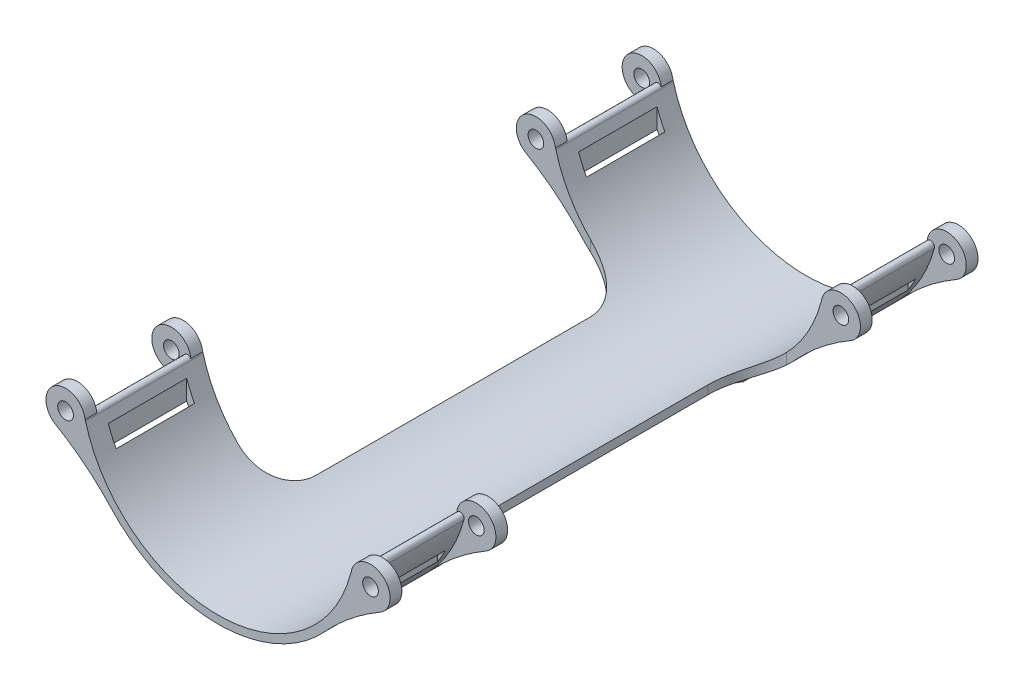
SolidWorks part; units mm, degrees
ref_plane "Front Plane" through (0, 0, 0) normal (0, 0, 1) x (1, 0, 0)
ref_plane "Top Plane" through (0, 0, 0) normal (0, 1, 0) x (1, 0, 0)
ref_plane "Right Plane" through (0, 0, 0) normal (1, 0, 0) x (0, 0, -1)
sketch "Sketch1" plane through (0, 0, 0) normal (0, 0, 1) x (1, 0, 0)
  line L0 (0, 0) -> (-33.8074, -9.0587) construction
  line L1 (33.8074, -9.0587) -> (0, 0) construction
  line L4 (-33.8074, -9.0587) -> (33.8074, -9.0587) construction
  arc A0 (33.8074, -9.0587) -> (-33.8074, -9.0587) centre (0, 0) cw
  arc A1 (35.7393, -9.5763) -> (-35.7393, -9.5763) centre (0, 0) cw
  arc A2 (33.8074, -9.0587) -> (35.7393, -9.5763) centre (34.7733, -9.3175) cw
  arc A3 (-33.8074, -9.0587) -> (-35.7393, -9.5763) centre (-34.7733, -9.3175) ccw
  dimension "D1" = 35
  dimension "D2" = 150
  dimension "D3" = 2
extrude "Boss-Extrude1" add sketch "Sketch1" along normal blind 150
sketch "Sketch2" plane through (0, 0, 0) normal (0, 1, 0) x (1, 0, 0)
  line L0 (0, 0) -> (0, -146.1851) construction
  line L1 (33.8074, -150) -> (33.8074, 0) construction
  line L2 (-55.1095, -30) -> (-15, -30)
  line L3 (-55.1095, -30) -> (-55.1095, -120)
  line L4 (-55.1095, -120) -> (-15, -120)
  line L5 (-15, -30) -> (-15, -120)
  line L6 (55.1095, -30) -> (15, -30)
  line L7 (55.1095, -30) -> (55.1095, -120)
  line L8 (55.1095, -120) -> (15, -120)
  line L9 (15, -30) -> (15, -120)
  line L10 (33.8074, -150) -> (33.8074, 0) construction
  line L12 (31, -5) -> (33, -5)
  line L13 (31, -5) -> (31, -25)
  line L14 (31, -25) -> (33, -25)
  line L15 (33, -5) -> (33, -25)
  line L20 (-31, -25) -> (-33, -25)
  line L21 (-33, -5) -> (-33, -25)
  line L22 (-31, -5) -> (-33, -5)
  line L23 (-31, -5) -> (-31, -25)
  line L24 (15, -75) -> (-94.2442, -75) construction
  line L25 (-31, -145) -> (-31, -125)
  line L26 (-31, -145) -> (-33, -145)
  line L27 (-33, -145) -> (-33, -125)
  line L28 (-31, -125) -> (-33, -125)
  line L29 (31, -125) -> (33, -125)
  line L30 (33, -145) -> (33, -125)
  line L31 (31, -145) -> (33, -145)
  line L32 (31, -145) -> (31, -125)
  point P13 (33.8074, -75)
  point P14 (15, -75)
  dimension "D1" = 30
  dimension "D2" = 90
  dimension "D3" = 20
  dimension "D4" = 5
  dimension "D5" = 33
  dimension "D6" = 2
extrude "Cut-Extrude1" cut sketch "Sketch2" against normal blind 120
sketch "Sketch3" plane through (0, 0, 0) normal (0, 0, -1) x (-1, 0, 0)
  line L0 (0, 0) -> (0, 24.5047) construction
  circle A0 centre (-38.8997, -9.3175) radius 2
  arc A2 (-33.8074, -9.0587) -> (33.8074, -9.0587) centre (0, 0) ccw construction
  circle A3 centre (-38.8997, -9.3175) radius 5
  circle A5 centre (-34.7733, -9.3175) radius 0.5155 construction
  circle A6 centre (38.8997, -9.3175) radius 2
  circle A7 centre (38.8997, -9.3175) radius 5
  dimension "D1" = 4
  dimension "D2" = 3
extrude "Boss-Extrude2" add sketch "Sketch3" against normal blind 3
sketch "Sketch4" plane through (0, 0, 30) normal (0, 0, 1) x (1, 0, 0)
  circle A0 centre (-38.8997, -9.3175) radius 2 construction
  circle A1 centre (-38.8997, -9.3175) radius 2
  circle A2 centre (38.8997, -9.3175) radius 2 construction
  circle A3 centre (38.8997, -9.3175) radius 2
  circle A4 centre (-38.8997, -9.3175) radius 5
  circle A5 centre (38.8997, -9.3175) radius 5
extrude "Boss-Extrude3" add sketch "Sketch4" against normal blind 3
pattern_linear "LPattern1" count 2 spacing 120 along (0, 0, 1) of "Boss-Extrude3", "Boss-Extrude2"
fillet "Fillet1" radius 60 8 edges at (-34.8928, -12.3083, 28.5) (-34.8928, -12.3083, 1.5) (34.8928, -12.3083, 1.5) (34.8928, -12.3083, 28.5) (34.8928, -12.3083, 121.5) (34.8928, -12.3083, 148.5) (-34.8928, -12.3083, 121.5) (-34.8928, -12.3083, 148.5)
sketch "Sketch5" plane through (0, 0, 120) normal (0, 0, -1) x (-1, 0, 0)
  line L0 (15, -33.8231) -> (15, -31.6228) construction
  line L1 (15, -34.167) -> (15, -31.6228)
  line L2 (-15, -33.8231) -> (-15, -31.6228) construction
  line L3 (-15, -33.9519) -> (-15, -31.6228)
  line L4 (15, -34.167) -> (15, -35.4917)
  line L5 (-15, -33.9519) -> (-15, -35.4577)
  arc A0 (15, -35.4577) -> (-15, -35.4577) centre (0, 0) cw
  arc A1 (-27.2721, -25.0047) -> (27.2721, -25.0047) centre (0, 0) ccw construction
  arc A2 (-33.8074, -9.0587) -> (33.8074, -9.0587) centre (0, 0) ccw construction
  arc A3 (-15, -31.6228) -> (15, -31.6228) centre (0, 0) ccw
  point P2 (0, 0)
  point P6 (0, 0)
  point P9 (15, -31.6228)
  point P14 (-15, -33.9519)
  point P15 (15, -31.6228)
  point P17 (-15, -31.6228)
  point P19 (-15, -31.6228)
  point P21 (15, -34.167)
  point P23 (0, 0)
  point P24 (-15, -31.6228)
  point P25 (-15, -35.4917)
  line M7 (-15, -33.8231) -> (-15, -31.6228)
  dimension "D1" = 1.5
extrude "Boss-Extrude4" add sketch "Sketch5" along normal mid plane 2 contours A3 L3 L5 A0 L4 L1 M7 region at (0, -35.6739, 120)
fillet "Fillet2" radius 20 2 edges at (0, -37, 121) (0, -37, 119)
pattern_linear "LPattern2" count 2 spacing 90 along (0, 0, -1) of "Fillet2", "Boss-Extrude4"
fillet "Fillet3" radius 10 4 edges at (-15, -32.7229, 30) (15, -32.7229, 30) (15, -32.7229, 120) (-15, -32.7229, 120)
